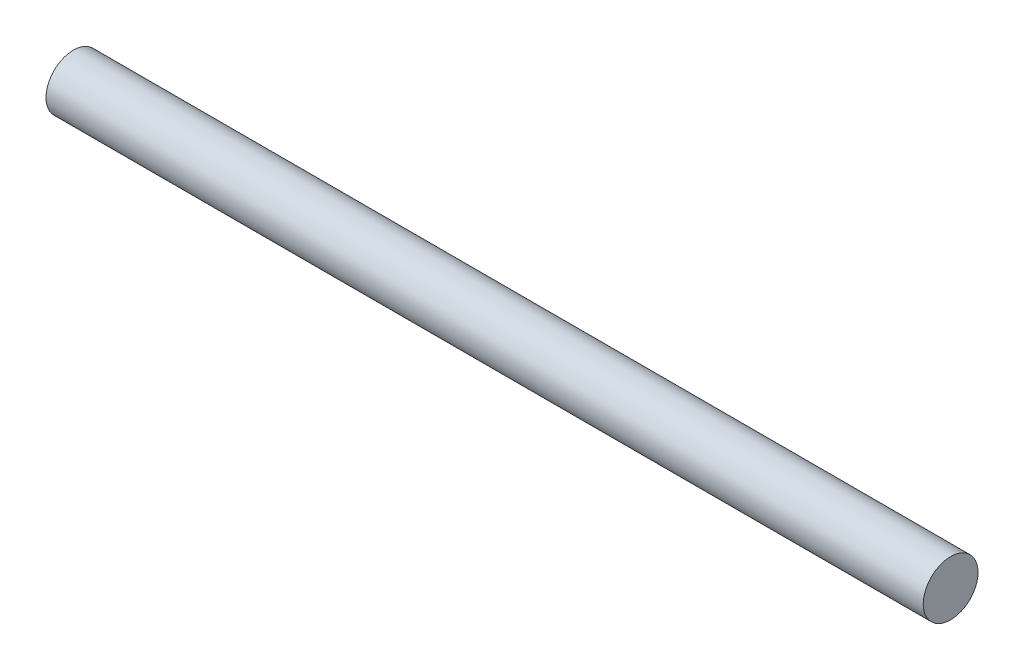
SolidWorks part; units mm, degrees
material "Cast Alloy Steel"
ref_plane "Front Plane" through (0, 0, 0) normal (0, 0, 1) x (1, 0, 0)
ref_plane "Top Plane" through (0, 0, 0) normal (0, 1, 0) x (1, 0, 0)
ref_plane "Right Plane" through (0, 0, 0) normal (1, 0, 0) x (0, 0, -1)
sketch "Sketch1" plane through (0, 0, 0) normal (1, 0, 0) x (0, 0, -1)
  circle A0 centre (0, 0) radius 4.7625
  dimension "D1" = 9.525
extrude "Boss-Extrude1" add sketch "Sketch1" along normal mid plane 152.4
